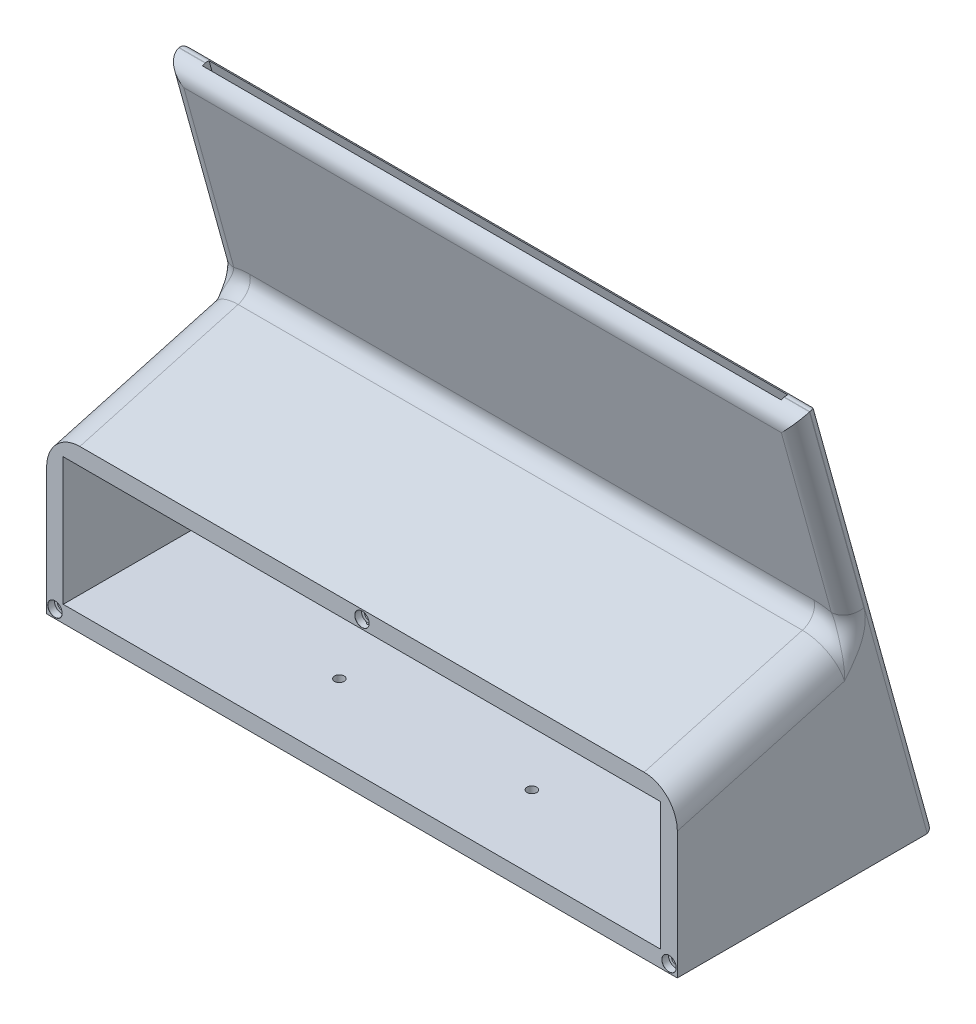
SolidWorks part; units mm, degrees
ref_plane "前视基准面" through (0, 0, 0) normal (0, 0, 1) x (1, 0, 0)
ref_plane "上视基准面" through (0, 0, 0) normal (0, 1, 0) x (1, 0, 0)
ref_plane "右视基准面" through (0, 0, 0) normal (1, 0, 0) x (0, 0, -1)
other "Configuration Table"
sketch "草图1" plane through (0, 0, 0) normal (1, 0, 0) x (0, 0, -1)
  line L0 (0, 0) -> (0, 126.4454) construction
  line L1 (-35, 0) -> (35, 0)
  line L3 (-35, 0) -> (-35, 48.6907)
  line L4 (-35, 48.6907) -> (17.5, 63.2227)
  line L5 (0, 126.4454) -> (17.5, 63.2227)
  line L6 (0, 126.4454) -> (6.8599, 128.3442)
  line L7 (6.8599, 128.3442) -> (42.3855, 0)
  line L8 (42.3855, 0) -> (35, 0)
  point P6 (0, 0)
  dimension "D1" = 70
  dimension "D2" = 131.2
extrude "凸台-拉伸1" add sketch "草图1" along normal blind 190
ref_plane "基准面1" through (0, 10.8973, -39.3691) normal (0, 0.2668, -0.9638) x (-1, 0, 0)
sketch "草图2" plane through (0, 10.8973, -39.3691) normal (0, 0.2668, -0.9638) x (-1, 0, 0)
  line L0 (-190, 121.8631) -> (0, -11.3071) construction
  line L1 (0, 121.8631) -> (-190, -11.3071) construction
  line L3 (-176.6, 104.238) -> (-13.4, 104.238)
  line L4 (-176.6, 104.238) -> (-176.6, 6.318)
  line L5 (-176.6, 6.318) -> (-13.4, 6.318)
  line L6 (-13.4, 104.238) -> (-13.4, 6.318)
  line L7 (-176.6, 104.238) -> (-13.4, 6.318) construction
  line L8 (-176.6, 6.318) -> (-13.4, 104.238) construction
  point P8 (-95, 55.278)
  dimension "D1" = 97.92
  dimension "D2" = 163.2
extrude "切除-拉伸1" cut sketch "草图2" against normal blind 1
ref_plane "基准面2" through (0, 10.6306, -38.4054) normal (0, 0.2668, -0.9638) x (-1, 0, 0)
sketch "草图3" plane through (0, 10.6306, -38.4054) normal (0, 0.2668, -0.9638) x (-1, 0, 0)
  line L0 (-176.6, 104.238) -> (-13.4, 6.318) construction
  line L1 (-13.4, 104.238) -> (-176.6, 6.318) construction
  line L2 (-95, 55.278) -> (-95, -0.722) construction
  line L3 (-180.5, 111.278) -> (-9.5, 111.278)
  line L4 (-180.5, 111.278) -> (-180.5, -0.722)
  line L5 (-180.5, -0.722) -> (-9.5, -0.722)
  line L6 (-9.5, 111.278) -> (-9.5, -0.722)
  line L7 (-180.5, 111.278) -> (-9.5, -0.722) construction
  line L8 (-180.5, -0.722) -> (-9.5, 111.278) construction
  line L9 (-103.5, -0.722) -> (-86.5, -0.722)
  line L10 (-103.5, -0.722) -> (-103.5, -8.5881)
  line L11 (-86.5, -0.722) -> (-86.5, -8.5881)
  line L12 (-86.5, -8.5881) -> (-103.5, -8.5881)
  line L13 (-180.5, 111.278) -> (-182.3453, 111.278)
  line L14 (-182.3453, 111.278) -> (-182.3453, 121.8631)
  line L15 (-190, 121.8631) -> (0, 121.8631) construction
  line L16 (-182.3453, 121.8631) -> (-7.9634, 121.8631)
  line L17 (-7.9634, 121.8631) -> (-7.9634, 111.278)
  line L18 (-7.9634, 111.278) -> (-9.5, 111.278)
  point P8 (-95, 55.278)
  point P18 (-95, -0.722)
  dimension "D1" = 112
  dimension "D2" = 171
  dimension "D3" = 17
extrude "切除-拉伸2" cut sketch "草图3" against normal offset from surface (18.4982 mm away) 5 contours L12 L10 L9 L11 up to face at (95, 0, -3.6928)
ref_plane "基准面3" through (0, 8.9985, -32.5092) normal (0, -0.2668, 0.9638) x (1, 0, 0)
extrude "切除-拉伸3" cut sketch "草图3<3>" against normal blind 2 contours L18 L17 L16 L14 L13 L3 region at (95.1543, 122.9767, -7.308)
sketch "草图3<3>" plane through (0, 10.6306, -38.4054) normal (0, 0.2668, -0.9638) x (-1, 0, 0) same geometry as "草图3"
extrude "切除-拉伸4" cut sketch "草图3<4>" against normal blind 2 contours L6 L3 L4 L5 region at (95, 63.9053, -23.659)
sketch "草图3<4>" plane through (0, 10.6306, -38.4054) normal (0, 0.2668, -0.9638) x (-1, 0, 0) same geometry as "草图3"
shell "抽壳1" thickness 5 removed face at (95, 24.3454, 35)
sketch "草图6" plane through (108.5, 0, 0) normal (1, 0, 0) x (0, 0, -1)
  line L0 (30.5178, 12.8862) -> (2.0272, 5)
  line L1 (2.0272, 5) -> (32.7007, 5)
  line L2 (32.7007, 5) -> (30.5178, 12.8862)
extrude "切除-拉伸5" cut sketch "草图6" against normal blind 40
sketch "草图9" plane through (0, 0, 0) normal (0, -1, 0) x (1, 0, 0)
  line L0 (0, 35) -> (190, -42.3855) construction
  line L2 (66, -10.1928) -> (124, -10.1928)
  line L3 (66, -10.1928) -> (66, 12.8072)
  line L4 (66, 12.8072) -> (124, 12.8072)
  line L5 (124, -10.1928) -> (124, 12.8072)
  line L6 (66, -15.1928) -> (124, 7.8072) construction
  line L7 (66, 7.8072) -> (124, -15.1928) construction
  point P4 (95, 1.3072)
  dimension "D1" = 58
  dimension "D2" = 23
fillet "圆角1" radius 10 2 edges at (0, 55.9567, 8.75) (190, 55.9567, 8.75)
fillet "圆角2" radius 5 6 edges at (95, 126.4454, 0) (190, 90.0152, -10.0838) (187.0711, 60.3999, -18.2813) (95, 63.2227, -17.5) (2.9289, 60.3999, -18.2813) (0, 90.0152, -10.0838)
fillet "圆角3" radius 2 8 edges at (95, 0, -42.3855) (190, 64.1721, -24.6227) (95, 128.3442, -6.8599) (0, 64.1721, -24.6227) (176.6, 64.1721, -24.6227) (95, 16.9864, -37.6837) (13.4, 64.1721, -24.6227) (95, 111.3578, -11.5617)
hole_wizard "大小六角凹头盖螺钉柱孔2" positions "草图12" profile "草图13" counterbore size "M2.5" standard "AS" end condition up to next
sketch "草图12" plane through (0, 0, 0) normal (0, -1, 0) x (-1, 0, 0)
  point P0 (-124, 10.1928)
  point P3 (-124, -12.8072)
  point P6 (-66, -12.8072)
  point P9 (-66, 10.1928)
sketch "草图13" plane through (124, 0, -10.1928) normal (1, 0, 0) x (0, 0, -1)
  line L0 (0, 0) -> (0, 5)
  line L1 (0, 5) -> (1.45, 5)
  line L3 (1.45, 5) -> (1.45, 2.5)
  line L4 (2.5, 2.5) -> (1.45, 2.5)
  line L5 (2.5, 2.5) -> (2.5, 0.0241)
  line L6 (2.5, 0.0241) -> (2.525, 0)
  line L7 (2.525, 0) -> (0, 0)
  line L8 (-2.5, 0.0241) -> (-2.525, 0) construction
  line L11 (0, -6.35) -> (0, 107.95) construction
  dimension "通孔孔直径" = 2.9
  dimension "通孔孔深度" = 5
  dimension "柱形沉头孔直径" = 5
  dimension "柱形沉头孔深度" = 2.5
  dimension "近端锥形沉头孔直径" = 5.05
  dimension "近端锥形沉头孔角度" = 92
sketch "草图14" plane through (0, 0, 35) normal (0, 0, 1) x (1, 0, 0)
  line L0 (5, 5) -> (0, 0) construction
  line L1 (2.5, 2.5) -> (0, 5) construction
  line L2 (190, 0) -> (185, 5) construction
  line L3 (187.5, 2.5) -> (190, 5) construction
  line L4 (180, 48.6907) -> (10, 48.6907)
  line L5 (0, 38.3147) -> (0, 0)
  line L6 (0, 0) -> (190, 0)
  line L7 (190, 0) -> (190, 38.3147)
  line L8 (180, 48.6907) -> (10, 48.6907)
  line L9 (0, 38.3147) -> (0, 0)
  line L10 (0, 0) -> (190, 0)
  line L11 (190, 0) -> (190, 38.3147)
  line L12 (95, 48.6907) -> (95, 43.5027) construction
  line L13 (185, 43.5027) -> (5, 43.5027) construction
  line L14 (95, 46.0967) -> (100.4338, 46.0967) construction
  line L15 (95, 46.0967) -> (88.6236, 46.0967) construction
  ellipse E2 centre (10, 38.3147) end of major axis (10, 48.6907) minor radius 10 (10, 48.6907) -> (0, 38.3147) ccw
  ellipse E3 centre (180, 38.3147) end of major axis (180, 27.9387) minor radius 10 (190, 38.3147) -> (180, 48.6907) ccw
  ellipse E4 centre (10, 38.3147) end of major axis (10, 48.6907) minor radius 10 (10, 48.6907) -> (0, 38.3147) ccw
  ellipse E5 centre (180, 38.3147) end of major axis (180, 27.9387) minor radius 10 (190, 38.3147) -> (180, 48.6907) ccw
  dimension "D1" = 0
hole_wizard "大小六角凹头盖螺钉柱孔3" positions "草图15" profile "草图17" counterbore size "M2" standard "AS"
sketch "草图15" plane through (0, 0, 35) normal (0, 0, 1) x (1, 0, 0)
  point P0 (2.5, 2.5)
  point P3 (95, 46.0967)
  point P6 (187.5, 2.5)
sketch "草图17" plane through (2.5, 2.5, 35) normal (1, 0, 0) x (0, -1, 0)
  line L0 (0, 0) -> (0, 10.721)
  line L1 (0, 10.721) -> (1.2, 10)
  line L2 (1.2, 10) -> (1.2, 2)
  line L3 (1.2, 2) -> (2.15, 2)
  line L5 (2.15, 2) -> (2.15, 0.0241)
  line L6 (2.15, 0.0241) -> (2.175, 0)
  line L7 (2.175, 0) -> (0, 0)
  line L8 (-2.15, 0.0241) -> (-2.175, 0) construction
  line L10 (0, 10.721) -> (-1.2, 10) construction
  line L11 (0, -6.35) -> (0, 107.95) construction
  dimension "孔直径" = 2.4
  dimension "孔深度" = 10
  dimension "锥形沉头孔直径" = 4.3
  dimension "锥形沉头孔深度" = 2
  dimension "近端锥形沉头孔直径" = 4.35
  dimension "近端锥形沉头孔角度" = 92
  dimension "导头角度" = 118
